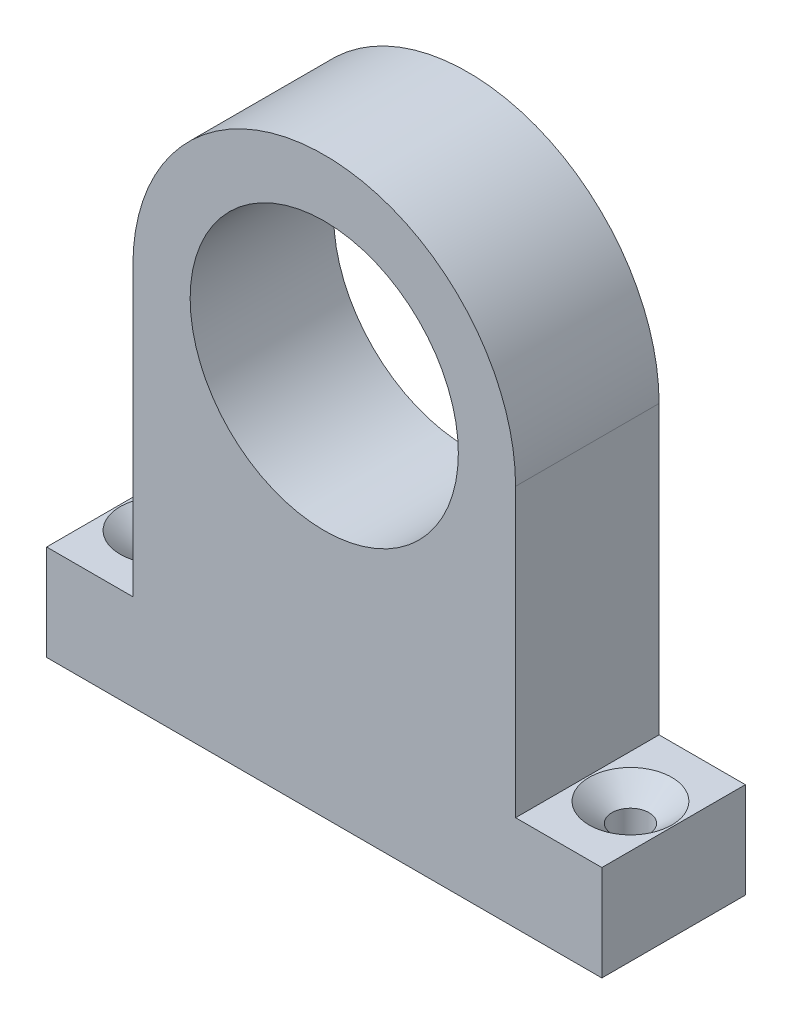
SolidWorks part; units mm, degrees
ref_plane "Front Plane" through (0, 0, 0) normal (0, 0, 1) x (1, 0, 0)
ref_plane "Top Plane" through (0, 0, 0) normal (0, 1, 0) x (1, 0, 0)
ref_plane "Right Plane" through (0, 0, 0) normal (1, 0, 0) x (0, 0, -1)
sketch "Sketch1" plane through (0, 19.05, 0) normal (0, 1, 0) x (1, 0, 0)
  line L0 (17.8, -59.4106) -> (-17.8, -59.4106) construction
  line L1 (-36.85, -78.4606) -> (36.85, -78.4606)
  line L2 (-36.85, -78.4606) -> (-36.85, -97.5106)
  line L3 (-36.85, -97.5106) -> (36.85, -97.5106)
  line L4 (36.85, -78.4606) -> (36.85, -97.5106)
  line L5 (-17.8, -113.4106) -> (17.8, -113.4106) construction
  line L6 (-17.8, -113.4106) -> (17.8, -113.4106) construction
  dimension "D1" = 19.05
  dimension "D2" = 19.05
  dimension "D3" = 19.05
  dimension "D4" = 19.05
extrude "Boss-Extrude2" add sketch "Sketch1" along normal blind 76.2
sketch "Sketch2" plane through (0, 0, 97.5106) normal (0, 0, 1) x (1, 0, 0)
  line L0 (-36.85, 95.25) -> (36.85, 95.25) construction
  line L1 (-36.85, 31.75) -> (36.85, 31.75)
  line L4 (0, 95.25) -> (0, 69.85) construction
  line L5 (-25.4, 69.85) -> (-25.4, 31.75)
  line L6 (25.4, 69.85) -> (25.4, 31.75)
  line L8 (-36.85, 19.05) -> (36.85, 19.05)
  line L9 (36.85, 19.05) -> (36.85, 95.25)
  line L10 (36.85, 95.25) -> (-36.85, 95.25)
  line L11 (-36.85, 95.25) -> (-36.85, 19.05)
  line L12 (-36.85, 19.05) -> (36.85, 19.05)
  line L13 (36.85, 19.05) -> (36.85, 95.25)
  line L14 (36.85, 95.25) -> (-36.85, 95.25)
  line L15 (-36.85, 95.25) -> (-36.85, 19.05)
  circle A0 centre (0, 69.85) radius 17.8 construction
  circle A1 centre (0, 69.85) radius 17.8
  circle A2 centre (0, 69.85) radius 25.4
  line M8 (36.85, 19.05) -> (36.85, 95.25)
  line M9 (36.85, 95.25) -> (-36.85, 95.25)
  line M10 (-36.85, 95.25) -> (-36.85, 19.05)
  dimension "D2" = 12.7
  dimension "D1" = 0
extrude "Cut-Extrude1" cut sketch "Sketch2" against normal through all contours A2 L14 L1 L5 M10 | A2 L6 L1 M8 M9 | A1 region at (-29.3017, 67.6713, 97.5106) region at (29.3017, 67.6713, 97.5106)
hole_wizard "CSK for #8 Flat Head Machine Screw (100)1" positions "Sketch3" profile "Sketch4" countersink size "#8" standard "ANSI Inch" end condition through all
sketch "Sketch3" plane through (0, 31.75, 0) normal (0, 1, 0) x (1, 0, 0)
  point P0 (-31.125, -87.9856)
  point P1 (31.125, -87.9856)
  point P3 (0, 0)
sketch "Sketch4" plane through (-31.125, 31.75, 87.9856) normal (1, 0, 0) x (0, 0, 1)
  line L0 (0, 0) -> (0, 12.7)
  line L1 (0, 12.7) -> (2.4574, 12.7)
  line L2 (2.4574, 12.7) -> (2.4574, 2.5416)
  line L3 (2.4574, 2.5416) -> (5.4864, 0)
  line L5 (5.4864, 0) -> (0, 0)
  line L6 (-2.4574, 2.5416) -> (-5.4864, 0) construction
  line L11 (0, -6.35) -> (0, 107.95) construction
  dimension "Thru Hole Dia." = 4.9149
  dimension "Thru Hole Depth" = 12.7
  dimension "Near C'Sink Dia." = 10.9728
  dimension "Near C'Sink Angle" = 100
